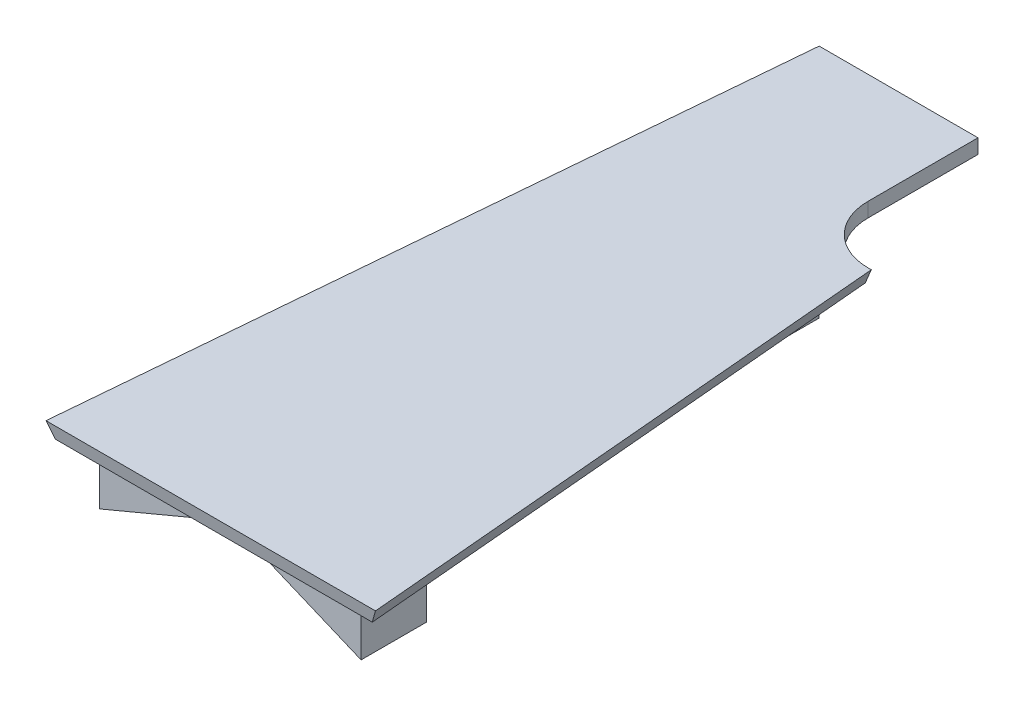
SolidWorks part; units mm, degrees
ref_plane "Ebene vorne" through (0, 0, 0) normal (0, 0, 1) x (1, 0, 0)
ref_plane "Ebene oben" through (0, 0, 0) normal (0, 1, 0) x (1, 0, 0)
ref_plane "Ebene rechts" through (0, 0, 0) normal (1, 0, 0) x (0, 0, -1)
sketch "Skizze1" plane through (0, 0, 0) normal (0, 1, 0) x (1, 0, 0)
  line L1 (-28.5, -61.5) -> (28.5, -61.5)
  line L2 (-28.5, -61.5) -> (-28.5, 61.5)
  line L3 (-28.5, 61.5) -> (28.5, 61.5)
  line L4 (28.5, -61.5) -> (28.5, 61.5)
  line L5 (-28.5, -61.5) -> (28.5, 61.5) construction
  line L6 (-28.5, 61.5) -> (28.5, -61.5) construction
  point P0 (0, 0)
  dimension "D1" = 57
  dimension "D2" = 123
extrude "Aufsatz-Linear austragen1" add sketch "Skizze1" along normal blind 2.5
sketch "Skizze2" plane through (28.5, 0, 0) normal (1, 0, 0) x (0, 0, -1)
  line L0 (-61.5, 2.5) -> (-61.5, 0)
  line L1 (55, 0) -> (-55, 0) construction
  line L2 (-61.5, 2.5) -> (-61.5, 0) construction
  line L3 (-61.5, 0) -> (-60.9686, 0)
  line L4 (-60.9686, 0) -> (-61.5, 2.5)
  dimension "D1" = 102
extrude "Schnitt-Linear austragen1" cut sketch "Skizze2" against normal through all
sketch "Skizze3" plane through (0, 2.5, 0) normal (0, 1, 0) x (1, 0, 0)
  line L0 (-28.5, -61.5) -> (-17.7389, 61.5)
  line L1 (28.5, 61.5) -> (-28.5, 61.5) construction
  line L2 (-17.7389, 61.5) -> (-28.5, 61.5)
  line L3 (-28.5, 61.5) -> (-28.5, -61.5)
  line L4 (28.5, -61.5) -> (17.7389, 61.5)
  line L5 (17.7389, 61.5) -> (28.5, 61.5)
  line L6 (28.5, 61.5) -> (28.5, -61.5)
  dimension "D1" = 95
  dimension "D2" = 95
extrude "Schnitt-Linear austragen2" cut sketch "Skizze3" against normal through all
ref_axis "Achse1" through (23.1194, 2.5, 0) along (0, -1, 0)
ref_plane "Ebene1" through (0.1756, 0, 2.0073) normal (0.0872, 0, 0.9962) x (0, -1, 0)
sketch "Skizze5" plane through (0.1756, 0, 2.0073) normal (0.0872, 0, 0.9962) x (0, -1, 0)
  line L0 (0.0086, 23.0315) -> (-2.5, 23.0315)
  line L1 (-2.5, 23.0315) -> (0, 23.0315) construction
  line L5 (0.0086, 23.0315) -> (0, 21.9959)
  line L6 (0, -33.659) -> (0, 23.0315) construction
  line L7 (0, 21.9959) -> (-2.5, 23.0315)
  line L8 (-2.5, -33.7516) -> (-2.5, 23.0315) construction
  dimension "D1" = 67.5
extrude "Schnitt-Linear austragen3" cut sketch "Skizze5" against normal through all and the other way through all
ref_axis "Achse2" through (-23.0962, -8.4274, -0.2657) along (0, 1, 0)
ref_plane "Ebene2" through (-0.1524, 0, 1.7416) normal (-0.0872, 0, 0.9962) x (0, 1, 0)
sketch "Skizze6" plane through (-0.1524, 0, 1.7416) normal (-0.0872, 0, 0.9962) x (0, 1, 0)
  line L1 (2.5, 23.0315) -> (0, 21.9959)
  line L2 (0, -55) -> (0, 55) construction
  line L3 (0, 21.9959) -> (0, 23.0315)
  line L4 (0, 23.0315) -> (2.5, 23.0315)
  line L5 (2.5, 23.0315) -> (2.5, -33.7516) construction
  dimension "D1" = 67.5
extrude "Schnitt-Linear austragen4" cut sketch "Skizze6" against normal through all and the other way through all
sketch "Skizze9" plane through (0, 0, 0) normal (0, -1, 0) x (1, 0, 0)
  line L6 (0, -61.5) -> (0, 60.9686) construction
  line L11 (16.6994, -61.5) -> (-16.6994, -61.5) construction
  line L12 (-27.414, 60.9686) -> (27.414, 60.9686) construction
  line L13 (0, 52.4686) -> (-26.6704, 52.4686) construction
  line L14 (-16.6994, -61.5) -> (-27.414, 60.9686) construction
  line L15 (-26.6704, 52.4686) -> (26.6704, 52.4686) construction
  line L16 (16.6994, -61.5) -> (27.414, 60.9686) construction
  line L17 (0, -19.5) -> (-20.3739, -19.5) construction
  line L18 (-20.3739, -19.5) -> (20.3739, -19.5) construction
  line L20 (22.6207, 58.1089) -> (-22.6207, 58.1089)
  line L21 (22.6207, 58.1089) -> (22.6207, 46.8283)
  line L22 (22.6207, 46.8283) -> (-22.6207, 46.8283)
  line L23 (-22.6207, 58.1089) -> (-22.6207, 46.8283)
  line L24 (22.6207, 58.1089) -> (-22.6207, 46.8283) construction
  line L25 (22.6207, 46.8283) -> (-22.6207, 58.1089) construction
  dimension "D1" = 42
  dimension "D2" = 8.5
extrude "Aufsatz-Linear austragen2" add sketch "Skizze9" along normal blind 13 contours L21 L20 L23 L22
sketch "Skizze11" plane through (0, 0, 46.8283) normal (0, 0, -1) x (-1, 0, 0)
  line L0 (-22.6207, -9.484) -> (0, 0)
  line L1 (-22.6207, -13) -> (-22.6207, 0) construction
  line L2 (-22.6207, 0) -> (22.6207, 0) construction
  line L3 (0, 0) -> (22.6207, -9.484)
  line L4 (22.6207, -13) -> (22.6207, 0) construction
  line L5 (22.6207, -9.484) -> (22.6207, -13)
  line L6 (22.6207, -13) -> (-22.6207, -13)
  line L7 (-22.6207, -13) -> (-22.6207, -9.484)
extrude "Schnitt-Linear austragen5" cut sketch "Skizze11" against normal blind 20
sketch "Skizze12" plane through (0, 0, 0) normal (0, -1, 0) x (1, 0, 0)
  line L0 (0, -61.5) -> (0, -2.1503) construction
  line L5 (16.6994, -61.5) -> (-16.6994, -61.5) construction
  line L6 (-20.3739, -19.5) -> (20.3739, -19.5) construction
  line L12 (-16.6994, -61.5) -> (-27.414, 60.9686) construction
  line L13 (16.6994, -61.5) -> (27.414, 60.9686) construction
  line L15 (18.0118, -15.2638) -> (-18.0118, -15.2638)
  line L16 (18.0118, -15.2638) -> (18.0118, -25.7362)
  line L17 (18.0118, -25.7362) -> (-18.0118, -25.7362)
  line L18 (-18.0118, -15.2638) -> (-18.0118, -25.7362)
  line L19 (18.0118, -15.2638) -> (-18.0118, -25.7362) construction
  line L24 (18.0118, -25.7362) -> (-18.0118, -15.2638) construction
  point P10 (0, -20.5)
  dimension "D2" = 41
extrude "Aufsatz-Linear austragen3" add sketch "Skizze12" along normal blind 5
sketch "Skizze13" plane through (0, 0, -25.7362) normal (0, 0, -1) x (-1, 0, 0)
  line L0 (-18.0118, -2.5) -> (-7.1831, 0)
  line L3 (-18.0118, -5) -> (-18.0118, 0) construction
  line L4 (18.0118, 0) -> (-18.0118, 0) construction
  line L5 (-7.1831, 0) -> (7.1831, 0)
  line L6 (7.1831, 0) -> (18.0118, -2.5)
  line L7 (18.0118, -5) -> (18.0118, 0) construction
  line L8 (18.0118, -2.5) -> (18.0118, -5)
  line L9 (18.0118, -5) -> (-18.0118, -5)
  line L10 (-18.0118, -5) -> (-18.0118, -2.5)
  dimension "D1" = 103
  dimension "D2" = 103
extrude "Schnitt-Linear austragen6" cut sketch "Skizze13" against normal blind 12
sketch "Skizze16" plane through (0, 0, 0) normal (0, -1, 0) x (1, 0, 0)
  line L0 (7.1831, -25.7362) -> (18.0118, -15.2638) construction
  line L1 (18.0118, -15.2638) -> (-18.0118, -15.2638) construction
  line L2 (-18.0118, -15.2638) -> (-7.1831, -25.7362) construction
  circle A0 centre (12.5975, -20.5) radius 3.1
  circle A1 centre (-12.5975, -20.5) radius 3.1
  dimension "D1" = 6.2
  dimension "D2" = 6.2
extrude "Schnitt-Linear austragen8" cut sketch "Skizze16" against normal blind 1.65 and the other way blind 0.5
ref_plane "Ebene7" through (0, -4.742, 0) normal (0, 1, 0) x (1, 0, 0)
sketch "Skizze17" plane through (0, -4.742, 0) normal (0, 1, 0) x (1, 0, 0)
  line L0 (22.6207, -58.1089) -> (11.3104, -46.8283) construction
  line L1 (0, -46.8283) -> (22.6207, -46.8283) construction
  line L2 (11.3104, -46.8283) -> (-11.3104, -58.1089) construction
  line L3 (-22.6207, -58.1089) -> (0, -58.1089) construction
  line L4 (-11.3104, -58.1089) -> (-22.6207, -46.8283) construction
  circle A0 centre (-16.9656, -52.4686) radius 3.1
  circle A1 centre (16.9656, -52.4686) radius 3.1
  dimension "D1" = 6.2
  dimension "D2" = 6.2
extrude "Schnitt-Linear austragen9" cut sketch "Skizze17" against normal blind 1 and the other way blind 1.15
sketch "Skizze18" plane through (0, 2.5, 0) normal (0, 1, 0) x (1, 0, 0)
  line L0 (17.7389, 61.5) -> (9.7389, 61.5)
  line L2 (9.7389, 61.5) -> (9.7389, 42.5)
  line L5 (20.2759, 32.5014) -> (17.7389, 61.5)
  line L6 (9.7389, 42.5) -> (9.7389, 42.4943)
  line L7 (19.8917, 32.4955) -> (20.2759, 32.5014)
  line L8 (17.7389, 61.5) -> (28.5, -61.5) construction
  line L9 (17.7389, 61.5) -> (-17.7389, 61.5) construction
  arc A1 (9.7389, 42.4943) -> (19.8917, 32.4955) centre (19.7389, 42.4943) ccw
  dimension "D1" = 10
  dimension "D4" = 0.3842
  dimension "D2" = 8
  dimension "D3" = 19
  dimension "D5" = 0
  dimension "D6" = 0
  dimension "D7" = 0.0057
extrude "Schnitt-Linear austragen10" cut sketch "Skizze18" against normal blind 10
